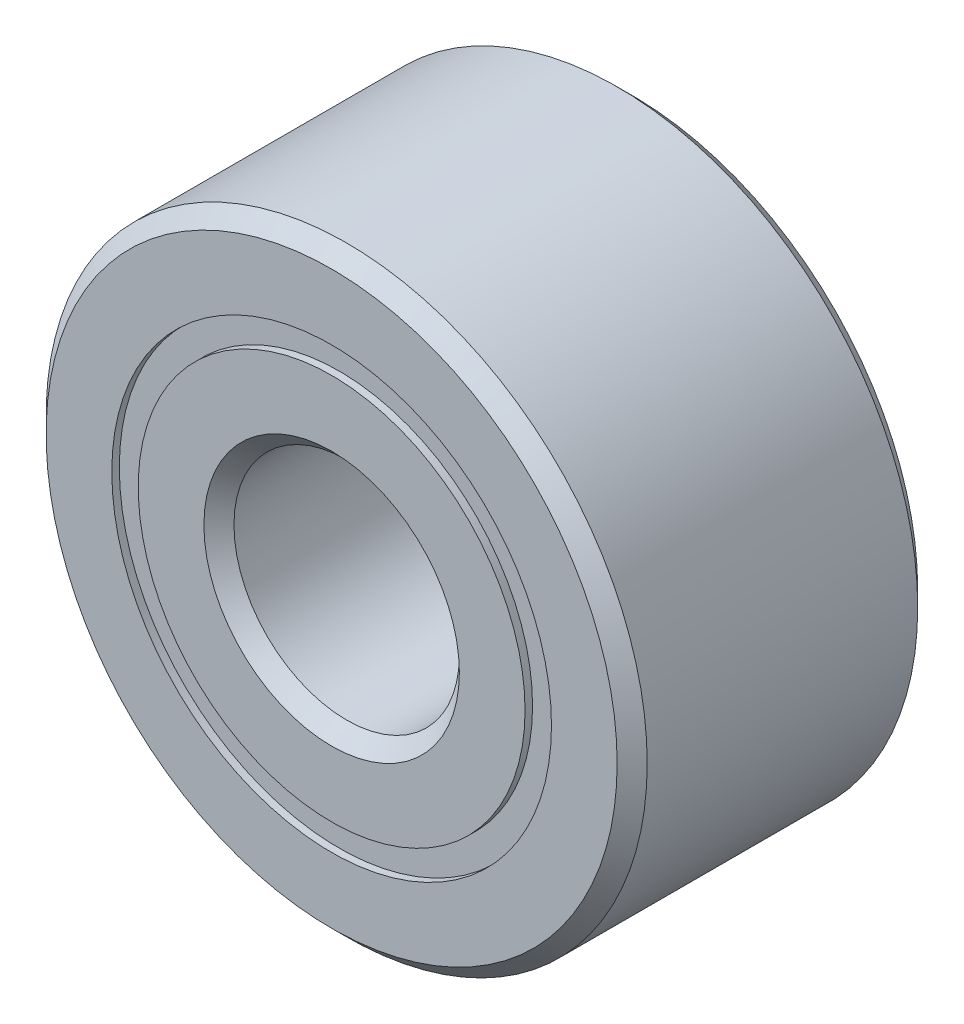
SolidWorks part; units mm, degrees
ref_plane "Front Plane" through (0, 0, 0) normal (0, 0, 1) x (1, 0, 0)
ref_plane "Top Plane" through (0, 0, 0) normal (0, 1, 0) x (1, 0, 0)
ref_plane "Right Plane" through (0, 0, 0) normal (1, 0, 0) x (0, 0, -1)
sketch "Sketch1" plane through (0, 0, 0) normal (1, 0, 0) x (0, 0, -1)
  line L0 (-2, 0) -> (2, 0) construction
  line L1 (0, 4) -> (0, -4) construction
  line L2 (1.8, 4) -> (-1.8, 4)
  line L3 (-1.8, 4) -> (-2, 3.8)
  line L4 (-2, 3.8) -> (-2, 2.9258)
  line L5 (-2, 2.9258) -> (-0.8889, 2.9258)
  line L6 (2, 2.9258) -> (0.8889, 2.9258)
  line L7 (2, 3.8) -> (2, 2.9258)
  line L8 (1.8, 4) -> (2, 3.8)
  line L9 (0, 4) -> (0, 2.75) construction
  line L10 (0, 2.75) -> (0, 1.5) construction
  arc A0 (-0.8889, 2.9258) -> (0.8889, 2.9258) centre (0, 2.75) cw
  point P14 (0, 1.5)
  dimension "D3" = 1.7778
  dimension "D1" = 45
  dimension "Width" = 4
  dimension "OD" = 8
  dimension "D2" = 0.2
  dimension "Shaft Dia" = 3
  dimension "D4" = 0.1758
revolve "Revolve1" add sketch "Sketch1" angle 360 about L0
sketch "Sketch3" plane through (0, 0, 0) normal (1, 0, 0) x (0, 0, -1)
  line L0 (-2, 2.5742) -> (-0.8889, 2.5742)
  line L1 (0, 4) -> (0, -4) construction
  line L2 (-2, 3.8) -> (-2, 2.9258) construction
  line L3 (-2, 2.5742) -> (-2, 1.7)
  line L4 (-1.8, 4) -> (-2, 3.8) construction
  line L5 (-2, 1.7) -> (-1.8, 1.5)
  line L6 (-1.8, 1.5) -> (1.8, 1.5)
  line L7 (1.8, 4) -> (1.8, -4) construction
  line L8 (1.8, 1.5) -> (2, 1.7)
  line L9 (2, -3.8) -> (2, 3.8) construction
  line L10 (2, 1.7) -> (2, 2.5742)
  line L11 (2, 2.5742) -> (0.8889, 2.5742)
  line L13 (1.8, 4) -> (2, 3.8) construction
  arc A0 (0.8889, 2.9258) -> (-0.8889, 2.9258) centre (0, 2.75) ccw construction
  arc A1 (0.8889, 2.5742) -> (-0.8889, 2.5742) centre (0, 2.75) cw
revolve "Revolve3" add sketch "Sketch3" angle 360 about L0
sketch "Sketch4" plane through (0, 0, 0) normal (1, 0, 0) x (0, 0, -1)
  line L0 (-0.9061, 2.75) -> (0.9061, 2.75)
  arc A2 (-0.9061, 2.75) -> (0.9061, 2.75) centre (0, 2.75) cw
  arc A3 (0.8889, 2.9258) -> (-0.8889, 2.9258) centre (0, 2.75) ccw construction
revolve "Revolve4" add sketch "Sketch4" angle 360 about L0
ref_axis "Axis1" through (0, 0, -2) along (0, 0, 1)
pattern_circular "CirPattern1" count 12 every 30 about axis through (0, 0, -2) along (0, 0, 1) of bodies 104
sketch "Sketch5" plane through (0, 0, 0) normal (1, 0, 0) x (0, 0, -1)
  line L0 (-2, 2.9258) -> (-0.8889, 2.9258) construction
  line L1 (-1.9, 2.9258) -> (-0.9061, 2.9258)
  line L2 (-1.9, 2.9258) -> (-1.9, 2.5742)
  line L3 (-1.9, 2.5742) -> (-0.9061, 2.5742)
  line L4 (-0.9061, 2.9258) -> (-0.9061, 2.5742)
  line L5 (-2, 2.5742) -> (-0.8889, 2.5742) construction
  line L6 (2, 2.9258) -> (0.8889, 2.9258) construction
  line L7 (1.9, 2.9258) -> (0.9061, 2.9258)
  line L8 (1.9, 2.9258) -> (1.9, 2.5742)
  line L9 (1.9, 2.5742) -> (0.9061, 2.5742)
  line L10 (0.9061, 2.9258) -> (0.9061, 2.5742)
  line L11 (2, 2.5742) -> (0.8889, 2.5742) construction
  line L12 (-1.8, 4) -> (-2, 3.8) construction
  point P18 (-1.9, 3.9)
revolve "Revolve5" add sketch "Sketch5" angle 360 about L0
sketch "Sketch6" plane through (0, 0, 0) normal (1, 0, 0) x (0, 0, -1)
  line L0 (2, 0) -> (-2, 0) construction
  line L1 (2, 2.9258) -> (0.9, 2.9258)
  line L2 (2, 2.9258) -> (2, 9.5)
  line L3 (2, 9.5) -> (0.9, 9.5)
  line L4 (0.9, 2.9258) -> (0.9, 9.5)
  dimension "Th" = 1.1
  dimension "Flange OD" = 19
revolve "Revolve6" [suppressed] add sketch "Sketch6" angle 360 about L0
equation "\"D2@Sketch1\" = \"Width@Sketch1\"*.05"
equation "\"D3@Sketch1\" = \"Width@Sketch1\"/2.25"
equation "\"D4@Sketch1\" = (((\"OD@Sketch1\"-\"Width@Sketch1\")/2)/3.25)/3.5"
equation "\"D2@CirPattern1\" = 360/\"Balls@CirPattern1\""
